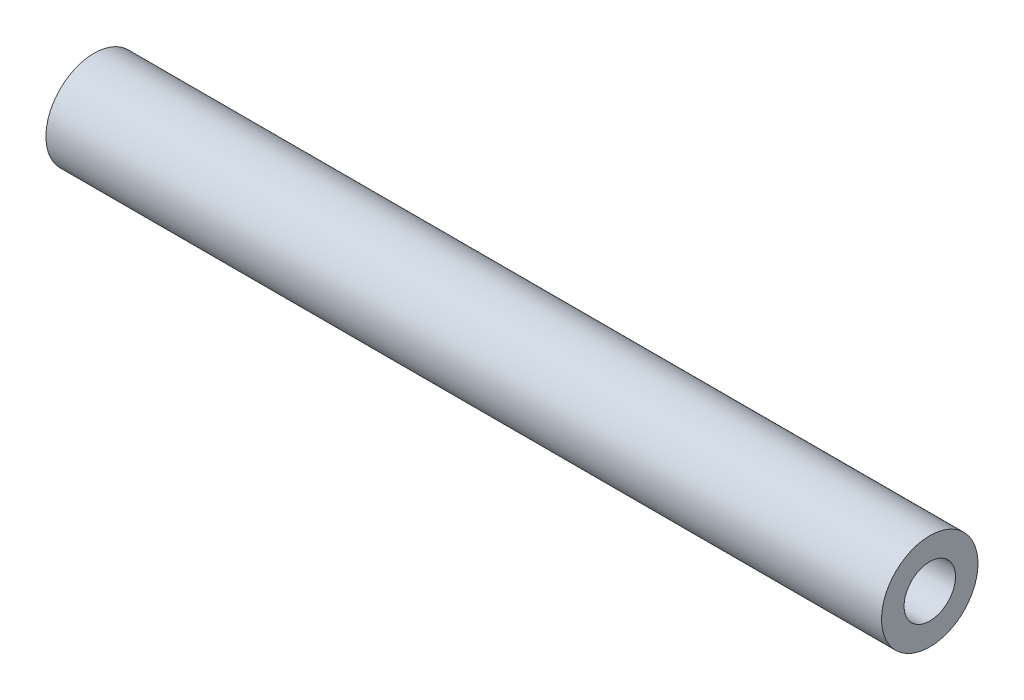
SolidWorks part; units mm, degrees
ref_plane "Front Plane" through (0, 0, 0) normal (0, 0, 1) x (1, 0, 0)
ref_plane "Top Plane" through (0, 0, 0) normal (0, 1, 0) x (1, 0, 0)
ref_plane "Right Plane" through (0, 0, 0) normal (1, 0, 0) x (0, 0, -1)
sketch "Sketch1" plane through (0, 0, 0) normal (1, 0, 0) x (0, 0, -1)
  circle A0 centre (0, 0) radius 4.7625
  circle A1 centre (0, 0) radius 2.54
  dimension "D1" = 9.525
  dimension "D2" = 5.08
extrude "Boss-Extrude1" add sketch "Sketch1" along normal blind 82.55
